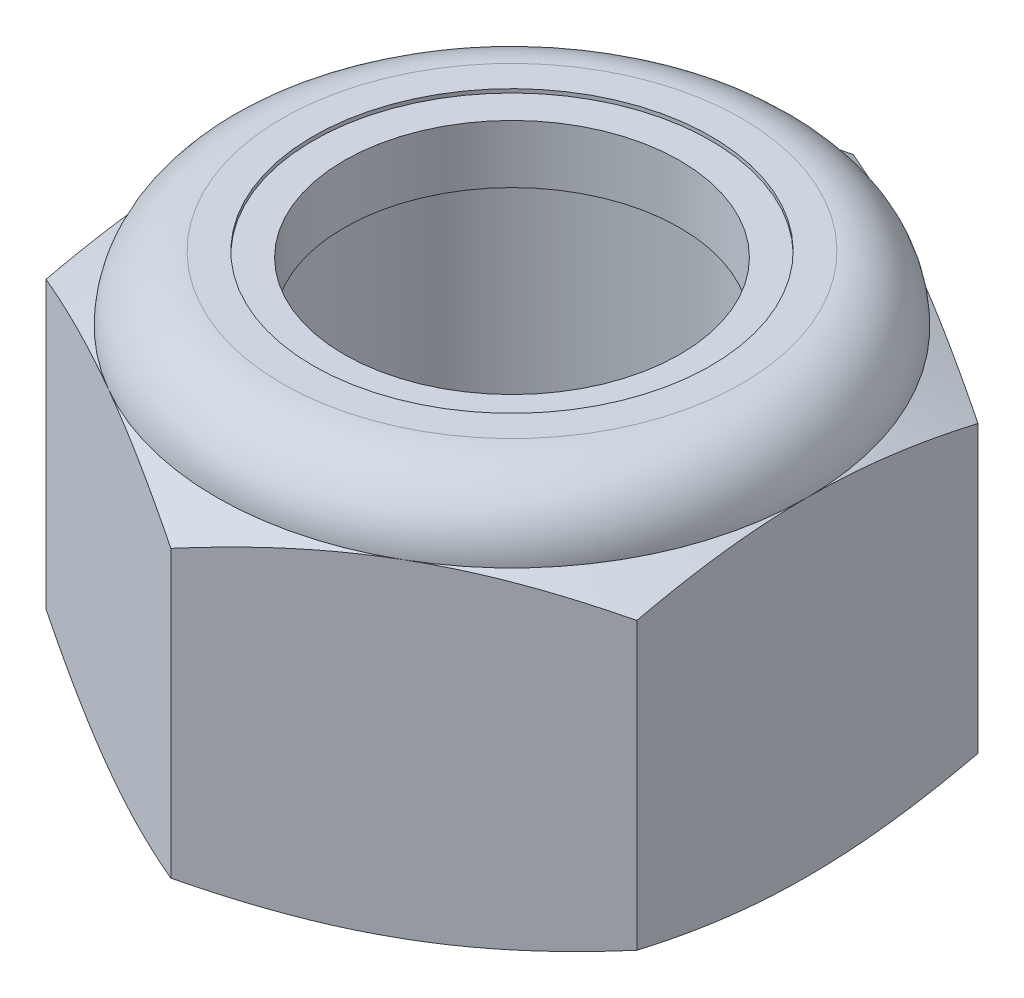
SolidWorks part; units mm, degrees
ref_plane "Front" through (0, 0, 0) normal (0, 0, 1) x (1, 0, 0)
ref_plane "Top" through (0, 0, 0) normal (0, 1, 0) x (1, 0, 0)
ref_plane "Right" through (0, 0, 0) normal (1, 0, 0) x (0, 0, -1)
sketch "Sketch1" plane through (0, 0, 0) normal (0, 1, 0) x (1, 0, 0)
  line L0 (0, 0) -> (5.6569, -5.6569) construction
  line L1 (0, 13.8564) -> (-12, 6.9282)
  line L2 (-12, 6.9282) -> (-12, -6.9282)
  line L3 (-12, -6.9282) -> (0, -13.8564)
  line L4 (0, -13.8564) -> (12, -6.9282)
  line L5 (12, -6.9282) -> (12, 6.9282)
  line L6 (12, 6.9282) -> (0, 13.8564)
  circle A0 centre (0, 0) radius 12 construction
  circle A1 centre (0, 0) radius 8
  point P12 (5.6569, -5.6569)
  dimension "Thread Dia" = 16
  dimension "Hex Flats" = 24
  dimension "D1" = 45
extrude "Extrude1" add sketch "Sketch1" along normal blind 16
chamfer "Chamfer1" distance 0.8 angle 45 1 edges at (0, 0, 8)
sketch "Sketch5" plane through (0, 0, 0) normal (1, 0, 0) x (0, 0, -1)
  line L0 (0, 0) -> (12, 0)
  line L1 (12, 0) -> (13.8564, 0.8657)
  line L2 (13.8564, 0.8657) -> (13.8564, 12.4677)
  line L3 (13.8564, 12.4677) -> (12, 13.3333)
  line L4 (9.3333, 16) -> (9.3333, 17.27)
  line L5 (9.3333, 17.27) -> (15.1264, 17.27)
  line L6 (15.1264, 17.27) -> (15.1264, -1.27)
  line L7 (15.1264, -1.27) -> (0, -1.27)
  line L8 (0, -1.27) -> (0, 0)
  line L9 (12, 13.3333) -> (12, 0) construction
  line L10 (6.9282, 16) -> (13.8564, 16) construction
  line L13 (13.8564, 6.6667) -> (15.1264, 6.6667) construction
  line L14 (13.8564, 16) -> (13.8564, 0) construction
  line L15 (0, 0) -> (0, 17.27) construction
  line L20 (0, 17.27) -> (9.3333, 17.27) construction
  arc A0 (12, 13.3333) -> (9.3333, 16) centre (9.3333, 13.3333) ccw
  dimension "D1" = 25
  dimension "D2" = 1.27
  dimension "D3" = 16
  dimension "D4" = 2.6667
revolve "Cut-Revolve3" cut sketch "Sketch5" angle 360 about L15
sketch "Sketch6" plane through (0, 0, 0) normal (1, 0, 0) x (0, 0, -1)
  line L0 (0, 13.3333) -> (11.8476, 13.3333)
  line L1 (9.3333, 15.8476) -> (8.0762, 15.8476)
  line L2 (0, 17.27) -> (0, 13.3333)
  line L3 (8.0762, 17.27) -> (0, 17.27)
  line L4 (0, 17.27) -> (9.3333, 17.27) construction
  line L5 (0, 0) -> (0, 17.27) construction
  line L6 (0, 17.27) -> (0, 0) construction
  line L7 (8.0762, 15.8476) -> (8.0762, 17.27)
  line L8 (9.3333, 16) -> (9.3333, 15.8476) construction
  line L9 (8.0762, 15.8476) -> (7.9238, 15.8476) construction
  line L21 (8, 15.8476) -> (8, 16) construction
  arc A0 (11.8476, 13.3333) -> (9.3333, 15.8476) centre (9.3333, 13.3333) ccw
  arc A1 (12, 13.3333) -> (9.3333, 16) centre (9.3333, 13.3333) ccw construction
  dimension "D1" = 0.1524
revolve "Cut-Revolve4" cut sketch "Sketch6" angle 360 about L6
sketch "Sketch7" plane through (0, 0, 0) normal (1, 0, 0) x (0, 0, -1)
  line L0 (6.8191, 13.4095) -> (11.7702, 13.4095)
  line L1 (9.3333, 15.7714) -> (6.8191, 15.7714)
  line L2 (6.8191, 15.7714) -> (6.8191, 13.4095)
  line L3 (6.8191, 13.4095) -> (0, 13.4095) construction
  line L4 (0, 13.4095) -> (0, 15.7714) construction
  line L5 (0, 15.7714) -> (6.8191, 15.7714) construction
  line L6 (6.8191, 13.4095) -> (6.8191, 13.3333) construction
  line L7 (0, 13.3333) -> (11.8476, 13.3333) construction
  line L8 (9.3333, 15.7714) -> (9.3333, 15.8476) construction
  line L10 (6.8191, 15.8476) -> (8.0762, 15.8476) construction
  line L11 (9.3333, 15.8476) -> (8.0762, 15.8476) construction
  arc A0 (11.7702, 13.4095) -> (9.3333, 15.7714) centre (9.3333, 13.3333) ccw
  arc A2 (11.8476, 13.3333) -> (9.3333, 15.8476) centre (9.3333, 13.3333) ccw construction
  dimension "D1" = 0.0762
revolve "Revolve2" add sketch "Sketch7" angle 360 about L4
ref_axis "Center Axis 1" through (0, 13.3333, 0) along (0, -1, 0)
sketch "Sketch12" [suppressed] plane through (0, 0, 0) normal (0, -1, 0) x (1, 0, 0)
  circle A0 centre (0, 0) radius 8
  circle A1 centre (0, 0) radius 8 construction
extrude "Boss-Extrude3" [suppressed] add sketch "Sketch12" against normal up to vertex
sketch "Sketch2" [suppressed] plane through (0, 0, 0) normal (1, 0, 0) x (0, 0, -1)
  line L1 (0, 0) -> (8, 0)
  line L2 (0, 0) -> (0, 15.8476)
  line L3 (0, 15.8476) -> (8, 15.8476)
  line L4 (8, 0) -> (8, 15.8476)
  line L7 (0, -8) -> (0, 0) construction
  line L11 (9.3333, 15.8476) -> (8.0762, 15.8476) construction
revolve "Revolve1" [suppressed] add sketch "Sketch2" angle 360 about L7
sketch "Sketch8" [suppressed] plane through (0, 0, 0) normal (0, -1, 0) x (1, 0, 0)
  circle A0 centre (0, 0) radius 8 construction
  circle A2 centre (0, 0) radius 8
curve "Helix/Spiral1" [suppressed] pitch 2 height 32 turns 16 parameters "Pitch"=2
sketch "Sketch9" [suppressed] plane through (0, 0, 0) normal (1, 0, 0) x (0, 0, -1)
  line L0 (8, -1.75) -> (8, 0)
  line L1 (8, -1.75) -> (6.701, -1)
  line L2 (6.701, -1) -> (6.701, -0.75)
  line L3 (6.701, -0.75) -> (8, 0)
  line L4 (-8, 0) -> (8, 0) construction
  line L5 (8, -0.875) -> (6.701, -0.875) construction
  line L6 (7.3505, -1.375) -> (7.3505, -0.375) construction
  dimension "D1" = 0.25
  dimension "D2" = 1
  dimension "D3" = 60
sweep "Cut-Sweep1" [suppressed] cut profiles "Sketch9" path "Helix/Spiral1"
combine bodies "Combine1" [suppressed] operation type subtract main body 135 bodies to subtract 132
sketch "Sketch14" [suppressed] plane through (0, 0, 0) normal (1, 0, 0) x (0, 0, -1)
  line L0 (0, 0) -> (0, 16) construction
  line L1 (8.0762, 16) -> (-8.0762, 16) construction
  line L2 (-8.8, 0) -> (-4, 4.8)
  line L4 (-8, 0) -> (-8.8, 0)
  line L9 (-4, 4.8) -> (0, 4.8)
  line L10 (0, 4.8) -> (0, 0)
  line L11 (0, 0) -> (-8, 0)
  line L12 (-4, 4.8) -> (-4, 0) construction
  dimension "D1" = 45
  dimension "D2" = 16
  dimension "D3" = 0.8
revolve "Cut-Revolve5" [suppressed] cut sketch "Sketch14" angle 360 about L0
equation "\"D4@Sketch5\"=\"Height@Extrude1\"/6"
equation "\"D3@Helix/Spiral1\"=2*\"Height@Extrude1\""
equation "\"D1@Sketch9\"=\"Pitch@Helix/Spiral1\"*.125"
equation "\"D2@Sketch9\"=\"Pitch@Helix/Spiral1\"*.50"
equation "\"D1@Chamfer1\"=.05*\"Thread Dia@Sketch1\""
equation "\"D2@Sketch14\"=\"Thread Dia@Sketch1\""
equation "\"D3@Sketch14\"=\"D1@Chamfer1\""
